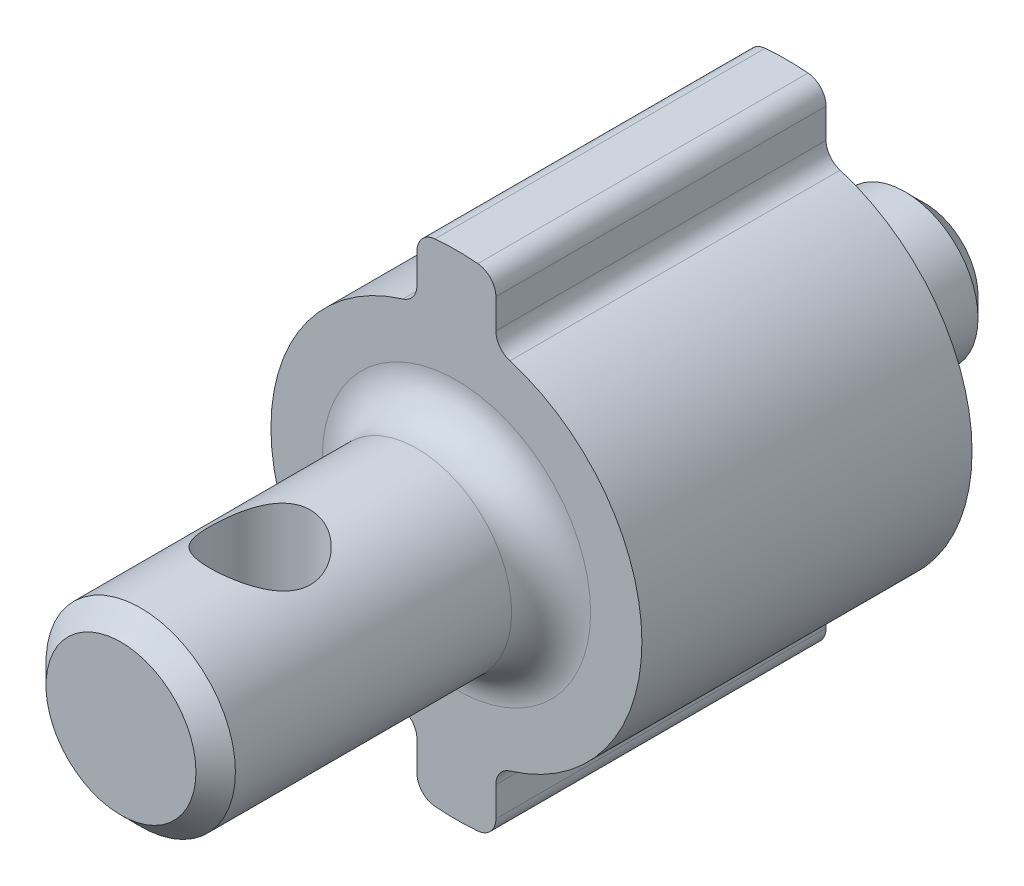
SolidWorks part; units mm, degrees
material "ABS"
ref_plane "Front Plane" through (0, 0, 0) normal (0, 0, 1) x (1, 0, 0)
ref_plane "Top Plane" through (0, 0, 0) normal (0, 1, 0) x (1, 0, 0)
ref_plane "Right Plane" through (0, 0, 0) normal (1, 0, 0) x (0, 0, -1)
sketch "Sketch1" plane through (0, 0, 0) normal (0, 0, 1) x (1, 0, 0)
  circle A0 centre (0, 0) radius 4.7
  dimension "D1" = 9.4
extrude "Boss-Extrude1" add sketch "Sketch1" along normal blind 11.8667
sketch "Sketch2" plane through (0, 0, 0) normal (0, 0, -1) x (-1, 0, 0)
  circle A0 centre (0, 0) radius 1.85
  dimension "D1" = 3.7
extrude "Cut-Extrude1" cut sketch "Sketch2" against normal blind 3.5 flip side to cut
sketch "Sketch3" plane through (0, 0, 11.8667) normal (0, 0, 1) x (1, 0, 0)
  line L0 (0, 6.25) -> (0, -6.25) construction
  line L1 (-6.25, 0) -> (6.25, 0) construction
  line L2 (-1, 4.5924) -> (-1, 6.1695)
  line L3 (1, 4.5924) -> (1, 6.1695)
  line L4 (1, -4.5924) -> (1, -6.1695)
  line L5 (-1, -4.5924) -> (-1, -6.1695)
  circle A0 centre (0, 0) radius 6.25
  circle A1 centre (0, 0) radius 4.7 construction
  circle A2 centre (0, 0) radius 4.7
  circle M7 centre (0, 0) radius 4.7
  dimension "D1" = 12.5
  dimension "D2" = 2
extrude "Boss-Extrude2" add sketch "Sketch3" against normal up to surface (8.3667 mm away) contours L3 A0 L2 M7 | L5 A0 L4 M7 region at (0, 5.4436, 11.8667) region at (0, -5.4436, 11.8667) up to face at (-1.85, 0, 3.5)
fillet "Fillet1" radius 0.5 8 edges at (-1, -4.5924, 7.6833) (-1, -6.1695, 7.6833) (1, -4.5924, 7.6833) (1, -6.1695, 7.6833) (1, 6.1695, 7.6833) (-1, 6.1695, 7.6833) (-1, 4.5924, 7.6833) (1, 4.5924, 7.6833)
fillet "Fillet2" radius 0.5 1 edges at (-1.85, 0, 3.5)
sketch "Sketch4" plane through (0, 0, 11.8667) normal (0, 0, 1) x (1, 0, 0)
  circle A0 centre (0, 0) radius 2.4
  dimension "D1" = 4.8
extrude "Boss-Extrude3" add sketch "Sketch4" along normal blind 8.5
fillet "Fillet3" radius 1 1 edges at (2.4, 0, 11.8667)
chamfer "Chamfer1" distance 0.5 angle 45 2 edges at (2.4, 0, 20.3667) (-1.85, 0, 0)
sketch "Sketch5" plane through (0, 0, 0) normal (0, 1, 0) x (1, 0, 0)
  line L0 (-1.9, -20.3667) -> (1.9, -20.3667) construction
  line L1 (-1.9, -20.3667) -> (1.9, -20.3667) construction
  line L2 (0, -20.3667) -> (0, -12.8667) construction
  line L3 (2.4, -12.8667) -> (-2.4, -12.8667) construction
  circle A0 centre (0, -16.8417) radius 1.275
  point P5 (0, -18.1167)
  dimension "D1" = 2.55
  dimension "D2" = 2.25
extrude "Cut-Extrude2" cut sketch "Sketch5" against normal through all and the other way through all
